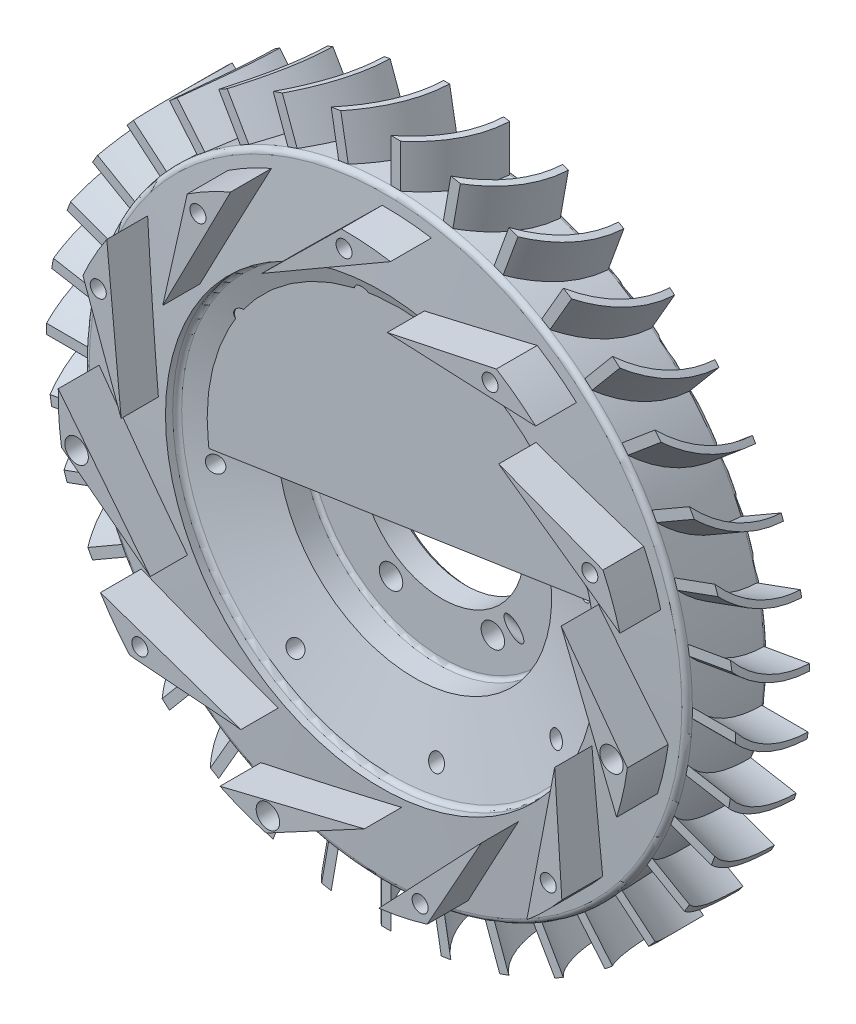
SolidWorks part; units mm, degrees
note: '?' marks a value the reader was unsure of.
material "6061-T6 (SS)"
ref_plane "Front Plane" through (0, 0, 0) normal (0, 0, 1) x (1, 0, 0)
ref_plane "Top Plane" through (0, 0, 0) normal (0, 1, 0) x (1, 0, 0)
ref_plane "Right Plane" through (0, 0, 0) normal (1, 0, 0) x (0, 0, -1)
sketch "Sketch1" plane through (0, 0, 0) normal (1, 0, 0) x (0, 0, -1)
  line L0 (0, 0) -> (-63.2335, 0) construction
  line L1 (0, 11) -> (0, 17)
  line L2 (0, 49.7227) -> (0, 0) construction
  line L3 (0, 17) -> (-1, 20)
  line L4 (-1, 20) -> (-3, 20)
  line L5 (-3, 20) -> (-3, 21)
  line L6 (-3, 21) -> (-3.82, 21)
  line L7 (-4.5, 21.68) -> (-4.5, 26.32)
  line L8 (-3.82, 27) -> (-3, 27)
  line L9 (-3, 27) -> (-3, 28)
  line L10 (-3, 28) -> (-7.565, 30.6356)
  line L11 (-9, 33.1211) -> (-9, 33.13)
  line L12 (-6.13, 36) -> (0, 36)
  line L13 (0, 36) -> (0, 37.6447)
  line L14 (-0.4826, 38.1444) -> (-10.0014, 38.4768)
  line L15 (-10.704, 37.8364) -> (-11.3, 27.5)
  line L16 (-11.3, 27.5) -> (-10.3799, 27.5)
  line L17 (-9.7262, 27.0074) -> (-7, 17.5)
  line L18 (-7, 17.5) -> (-4, 17.5)
  line L19 (-3.5, 17) -> (-3.5, 10.5)
  line L20 (-3.5, 10.5) -> (-0.5, 10.5)
  line L21 (-10.6657, 38.5) -> (-47.1745, 38.5) construction
  line L22 (-10.6657, 38.5) -> (-10.6657, 56.5681) construction
  line L23 (-0.5, 10.5) -> (0, 11)
  arc A0 (-9, 33.13) -> (-6.13, 36) centre (-6.13, 33.13) cw
  arc A1 (-7.565, 30.6356) -> (-9, 33.1211) centre (-6.13, 33.1211) cw
  arc A2 (-10.0014, 38.4768) -> (-10.704, 37.8364) centre (-10.0251, 37.7972) ccw
  arc A3 (-10.3799, 27.5) -> (-9.7262, 27.0074) centre (-10.3799, 26.82) cw
  arc A4 (-4.5, 26.32) -> (-3.82, 27) centre (-3.82, 26.32) cw
  arc A5 (-3.82, 21) -> (-4.5, 21.68) centre (-3.82, 21.68) cw
  arc A6 (0, 37.6447) -> (-0.4826, 38.1444) centre (-0.5, 37.6447) ccw
  arc A7 (-4, 17.5) -> (-3.5, 17) centre (-4, 17) cw
  point P3 (0, 10.5)
  dimension "D22" = 2.87
  dimension "D23" = 0.68
  dimension "D24" = 0.5
  dimension "D1" = 2
  dimension "D2" = 21
  dimension "D3" = 35
  dimension "D4" = 55
  dimension "D5" = 40
  dimension "D6" = 42
  dimension "D7" = 54
  dimension "D8" = 56
  dimension "D9" = 72
  dimension "D10" = 3.3
  dimension "D11" = 77
  dimension "D12" = 3.5
  dimension "D13" = 1
  dimension "D14" = 3
  dimension "D15" = 3.5
  dimension "D16" = 106
  dimension "D17" = 3
  dimension "D18" = 1.5
  dimension "D19" = 9
  dimension "D20" = 11.3
  dimension "D21" = 30
revolve "Revolve3" add sketch "Sketch1" angle 360 about L0
ref_axis "Axis1" through (0, 0, 3.5) along (0, 0, -1)?
ref_plane "Plane1" through (0, 0, 16) normal (0, 0, 1) x (1, 0, 0)
sketch "Sketch3" plane through (0, 0, 16) normal (0, 0, 1) x (1, 0, 0)
  line L0 (0, 0) -> (-10.486, 26.5008) construction
  line L1 (-10.486, 26.5008) -> (-0.3436, 36.4984)
  line L2 (-10.486, 26.5008) -> (5.9338, 36.0144)
  line L3 (0, 0) -> (0, 45.8696) construction
  circle A0 centre (0, 0) radius 28.5 construction
  arc A1 (5.9338, 36.0144) -> (-0.3436, 36.4984) centre (0, 0) ccw
  circle A2 centre (0, 34.5) radius 1.6644 construction
  dimension "D1" = 57
  dimension "D2" = 73
  dimension "D3" = 14.5
  dimension "D4" = 67
  dimension "D5" = 34.5
  dimension "D6" = 21.588
extrude "wedge" add sketch "Sketch3" against normal up to surface (5.2189 mm away)
hole_wizard "M2.5x0.45 Tapped Hole1" positions "Sketch5" profile "Sketch4" tap size "M2.5x0.45" standard "Ansi Metric" end condition through all
sketch "Sketch5" plane through (0, 0, 16) normal (0, 0, 1) x (1, 0, 0)
  point P0 (0, 34.5)
  dimension "D1" = 34.5
sketch "Sketch4" plane through (0, 34.5, 16) normal (1, 0, 0) x (0, -1, 0)
  line L0 (0, 0) -> (0, 16)
  line L1 (0, 16) -> (1.025, 16)
  line L2 (1.025, 16) -> (1.025, 0)
  line L5 (1.025, 0) -> (0, 0)
  line L11 (0, -6.35) -> (0, 107.95) construction
  dimension "Thread Major Dia." = 2.05
  dimension "Thru Tap Drill Depth" = 16
pattern_circular "CirPattern1" count 11 over 360 about axis through (0, 0, 0) along (0, 0, 1) of "M2.5x0.45 Tapped Hole1", "wedge"
hole_wizard "Ø3.0 (3) Diameter Hole1" positions "Sketch7" profile "Sketch6" hole size "Ø3.0" standard "Ansi Metric" end condition through all
sketch "Sketch7" plane through (0, 0, 16) normal (0, 0, 1) x (1, 0, 0)
  point P0 (-34.1488, -4.9099)
  point P1 (34.1488, -4.9099)
  point P4 (-9.7198, -33.1025)
sketch "Sketch6" plane through (-34.1488, -4.9099, 16) normal (1, 0, 0) x (0, -1, 0)
  line L0 (0, 0) -> (0, 16)
  line L1 (0, 16) -> (1.5, 16)
  line L2 (1.5, 16) -> (1.5, 0)
  line L5 (1.5, 0) -> (0, 0)
  line L11 (0, -6.35) -> (0, 107.95) construction
  dimension "Thru Hole Dia." = 3
  dimension "Thru Hole Depth" = 16
hole_wizard "Ø3.0 (3) Diameter Hole2" positions "Sketch9" profile "Sketch8" hole size "Ø3.0" standard "Ansi Metric"
sketch "Sketch9" plane through (0, 0, 3.5) normal (0, 0, 1) x (1, 0, 0)
  circle A0 centre (0, 0) radius 13 construction
  point P0 (-13, 0)
  dimension "D1" = 26
sketch "Sketch8" plane through (-13, 0, 3.5) normal (1, 0, 0) x (0, -1, 0)
  line L0 (0, 0) -> (0, 8.5213)
  line L1 (0, 8.5213) -> (1.5, 7.62)
  line L2 (1.5, 7.62) -> (1.5, 0)
  line L5 (1.5, 0) -> (0, 0)
  line L10 (0, 8.5213) -> (-1.5, 7.62) construction
  line L11 (0, -6.35) -> (0, 107.95) construction
  dimension "Hole Dia." = 3
  dimension "Hole Depth" = 7.62
  dimension "Drill Angle" = 118
pattern_circular "CirPattern2" count 6 over 360 about axis through (0, 0, 0) along (0, 0, 1) of "Ø3.0 (3) Diameter Hole2"
ref_plane "Plane2" through (36, 0, 0) normal (1, 0, 0) x (0, 0, -1)
sketch "Sketch10" plane through (36, 0, 0) normal (1, 0, 0) x (0, 0, -1)
  line L0 (0, 0) -> (-25.1711, 0) construction
  line L1 (-3.5, 0) -> (-0.5, 0) construction
  line L3 (-0.5129, -5.6633) -> (-0.4826, -4.8638)
  line L4 (-10.0014, 0) -> (-10.0014, -1.2406)
  line L7 (-10.0014, 38.4768) -> (-10.0014, -38.4768) construction
  line L8 (-0.4826, 38.1444) -> (-0.4826, -38.1444) construction
  arc A0 (-10.0014, 0) -> (-0.4826, -4.8638) centre (0, 7.827) ccw
  arc A1 (-10.0014, -1.2406) -> (-0.5129, -5.6633) centre (0, 7.827) ccw
  arc A3 (-10.6314, -0.493) -> (-0.5129, -5.6633) centre (0, 7.827) ccw construction
  dimension "D1" = 12.7
  dimension "D3" = 0.8
extrude "fin" add sketch "Sketch10" along normal blind 9
pattern_circular "CirPattern3" count 36 over 360 about axis through (0, 0, 0) along (0, 0, 1) of "fin"
sketch "Sketch12" plane through (0, 0, 0) normal (0, 0, 1) x (1, 0, 0)
  circle A0 centre (0, 0) radius 44
  dimension "D1" = 88
extrude "fin trim" cut sketch "Sketch12" along normal through all flip side to cut
hole_wizard "CBORE for M2.5 SHCS1" positions "Sketch14" profile "Sketch13" counterbore size "M2.5" standard "Ansi Metric" end condition through all
sketch "Sketch14" plane through (35.8042, 10.5319, 0) normal (0, 0, -1) x (-1, 0, 0)
  point P0 (45.524, -43.6344)
  point P18 (69.953, -15.4417)
  point P21 (1.6554, -15.4417)
sketch "Sketch13" plane through (-9.7198, -33.1025, 0) normal (1, 0, 0) x (0, 1, 0)
  line L0 (0, 0) -> (0, 16)
  line L1 (0, 16) -> (1.45, 16)
  line L3 (1.45, 16) -> (1.45, 9)
  line L4 (1.45, 9) -> (3, 9)
  line L5 (3, 9) -> (3, 0)
  line L7 (3, 0) -> (0, 0)
  line L11 (0, -6.35) -> (0, 107.95) construction
  dimension "Thru Hole Dia." = 2.9
  dimension "Thru Hole Depth" = 16
  dimension "C'Bore Dia." = 6
  dimension "C'Bore Depth" = 9
sketch "Sketch16" plane through (0, 0, 3.5) normal (0, 0, 1) x (1, 0, 0)
  line L0 (9.1924, -9.1924) -> (0, 0) construction
  line L1 (0, 0) -> (59.56, 0) construction
  line L2 (9.1924, -9.1924) -> (51.1817, 32.7969) construction
  dimension "D1" = 45
  dimension "D2" = 13
ref_plane "Plane3" through (5.8226, -5.8226, -4.7542) normal (-0.6124, 0.6124, 0.5) x (0.75, 0.25, 0.6124)
sketch "Sketch17" plane through (5.8226, -5.8226, -4.7542) normal (-0.6124, 0.6124, 0.5) x (0.75, 0.25, 0.6124)
  circle A0 centre (6.7395, -6.7395) radius 0.8
  dimension "D1" = 1.6
extrude "lube hole" cut sketch "Sketch17" against normal through all and the other way through all
ref_axis "Axis2" through (48.4, 0, 0) along (-1, 0, 0)?
ref_plane "Plane4" through (0, 0, 0) normal (0, 0.1736, 0.9848) x (1, 0, 0)
sketch "Sketch18" plane through (0, 0, 0) normal (0, -0.1736, -0.9848) x (1, 0, 0)
  line L0 (3.524, 33.7259) -> (9.4993, -23.1249) construction
  line L1 (6.5559, -24.1251) -> (3.524, 33.7259) construction
  line L2 (3.524, 33.7259) -> (3.524, -24.7504) construction
  line L3 (0, 0) -> (0, 8.6953) construction
  line L4 (4.453, 37.5491) -> (4.8066, 30.8016) construction
  line L5 (2.5951, 29.9026) -> (4.453, 37.5491) construction
  line L6 (2.5951, 29.9026) -> (2.1935, 37.5653) construction
  circle A0 centre (0, 0) radius 25 construction
  dimension "D2" = 50
  dimension "D1" = 3
  dimension "D3" = 3
  dimension "D5" = 3.7264
ref_axis "Hole rotation axis" through (3.524, -33.2135, 5.8564) along (0, 0.1736, 0.9848)?
ref_plane "air hole plane" through (0, 0, 0) normal (0, -0.9848, 0.1736) x (1, 0, 0)
hole_wizard "Ø2.0 (2) Diameter Hole3" positions "Sketch21" profile "Sketch20" hole size "Ø2.0" standard "Ansi Metric"
sketch "Sketch21" plane through (0, 0, 0) normal (0, -0.9848, 0.1736) x (1, 0, 0)
  line L0 (3.524, 0) -> (3.524, 49.6932) construction
  point P0 (3.524, 7.5)
  dimension "D1" = 7.5
sketch "Sketch20" plane through (3.524, 1.3024, 7.3861) normal (1, 0, 0) x (0, -0.1736, -0.9848)
  line L0 (0, 0) -> (0, 23.6009)
  line L1 (0, 23.6009) -> (1, 23)
  line L2 (1, 23) -> (1, 0)
  line L5 (1, 0) -> (0, 0)
  line L10 (0, 23.6009) -> (-1, 23) construction
  line L11 (0, -6.35) -> (0, 107.95) construction
  dimension "Hole Dia." = 2
  dimension "Hole Depth" = 23
  dimension "Drill Angle" = 118
pattern_circular "CirPattern4" count 3 every 3 about axis through (3.524, -33.2135, 5.8564) along (0, 0.1736, 0.9848) of "Ø2.0 (2) Diameter Hole3"
hole_wizard "M2.5x0.45 Tapped Hole2" positions "Sketch23" profile "Sketch22" tap size "M2.5x0.45" standard "Ansi Metric"
sketch "Sketch23" plane through (0, 0, 4.5) normal (0, 0, -1) x (-1, 0, 0)
  line L0 (0, 0) -> (4.6822, 23.5388) construction
  line L1 (0, 0) -> (0, 48.1069) construction
  point P0 (4.6822, 23.5388)
  dimension "D1" = 24
  dimension "D2" = 11.25
sketch "Sketch22" plane through (-4.6822, 23.5388, 4.5) normal (1, 0, 0) x (0, 1, 0)
  line L0 (0, 0) -> (0, 6.9659)
  line L1 (0, 6.9659) -> (1.025, 6.35)
  line L2 (1.025, 6.35) -> (1.025, 0)
  line L5 (1.025, 0) -> (0, 0)
  line L10 (0, 6.9659) -> (-1.025, 6.35) construction
  line L11 (0, -6.35) -> (0, 107.95) construction
  dimension "Tap Drill Dia." = 2.05
  dimension "Tap Drill Depth" = 6.35
  dimension "Drill Angle" = 118
pattern_circular "CirPattern5" count 8 over 360 about axis through (0, 0, 0) along (0, 0, 1) of "M2.5x0.45 Tapped Hole2"
